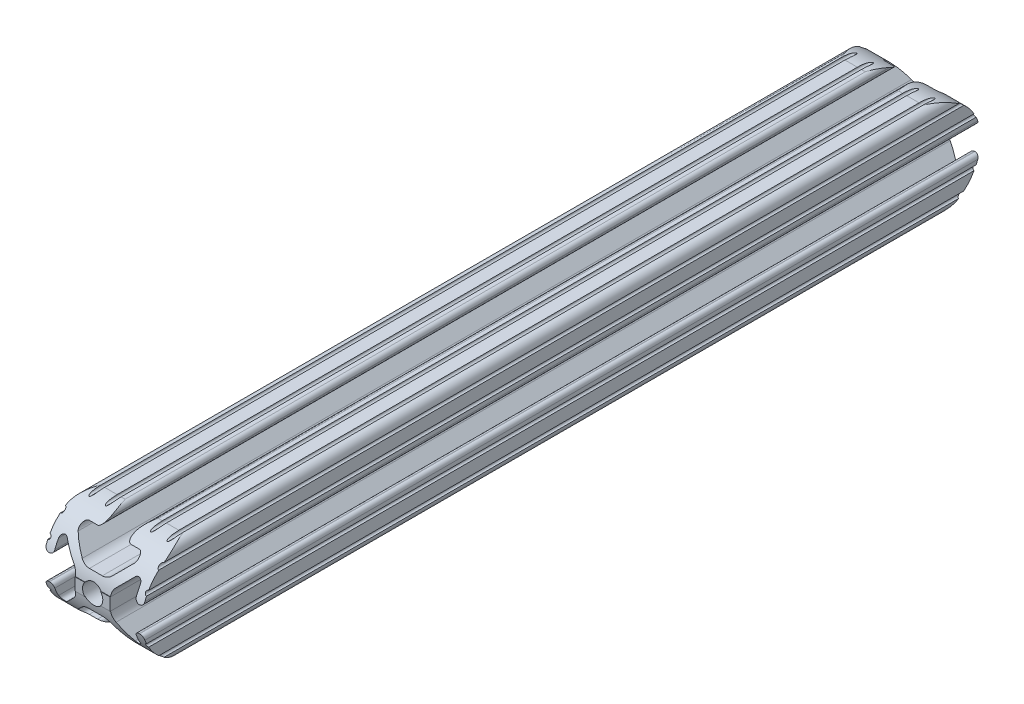
SolidWorks part; units mm, degrees
material "6061 Alloy"
ref_plane "Front Plane" through (0, 0, 0) normal (0, 0, 1) x (1, 0, 0)
ref_plane "Top Plane" through (0, 0, 0) normal (0, 1, 0) x (1, 0, 0)
ref_plane "Right Plane" through (0, 0, 0) normal (1, 0, 0) x (0, 0, -1)
sketch "Sketch1" plane through (0, 0, 0) normal (0, 0, 1) x (1, 0, 0)
  line L88 (-7.1797, -8.6452) -> (-3.9523, -5.4237)
  line L89 (-1.7093, -4.4958) -> (1.7093, -4.4958)
  line L90 (3.9523, -5.4237) -> (7.1797, -8.6452)
  line L91 (6.4164, -10.4902) -> (4.2875, -10.4902)
  line L92 (3.2385, -11.5392) -> (3.2385, -11.651)
  line L93 (4.2875, -12.7) -> (5.3171, -12.7)
  line L94 (6.3331, -12.7) -> (9.5504, -12.7)
  line L95 (12.7, -9.5504) -> (12.7, -6.3331)
  line L96 (12.7, -5.3171) -> (12.7, -4.2875)
  line L97 (11.651, -3.2385) -> (11.5392, -3.2385)
  line L98 (10.4902, -4.2875) -> (10.4902, -6.4021)
  line L99 (8.7371, -7.1294) -> (5.441, -3.8408)
  line L100 (4.5085, -1.5932) -> (4.5085, 1.5932)
  line L101 (5.441, 3.8408) -> (8.7371, 7.1294)
  line L102 (10.4902, 6.4021) -> (10.4902, 4.2875)
  line L103 (11.5392, 3.2385) -> (11.651, 3.2385)
  line L104 (12.7, 4.2875) -> (12.7, 5.3171)
  line L105 (12.7, 6.3331) -> (12.7, 9.5504)
  line L106 (9.5504, 12.7) -> (6.3331, 12.7)
  line L107 (5.3171, 12.7) -> (4.2875, 12.7)
  line L108 (3.2385, 11.651) -> (3.2385, 11.5392)
  line L109 (4.2875, 10.4902) -> (6.4768, 10.4902)
  line L110 (7.207, 8.7244) -> (3.8983, 5.4232)
  line L111 (1.6558, 4.4958) -> (-1.6558, 4.4958)
  line L112 (-3.8983, 5.4232) -> (-7.207, 8.7244)
  line L113 (-6.4768, 10.4902) -> (-4.2875, 10.4902)
  line L114 (-3.2385, 11.5392) -> (-3.2385, 11.651)
  line L115 (-4.2875, 12.7) -> (-5.3171, 12.7)
  line L116 (-6.3331, 12.7) -> (-9.5504, 12.7)
  line L117 (-12.7, 9.5504) -> (-12.7, 6.3331)
  line L118 (-12.7, 5.3171) -> (-12.7, 4.2875)
  line L119 (-11.651, 3.2385) -> (-11.5392, 3.2385)
  line L120 (-10.4902, 4.2875) -> (-10.4902, 6.4021)
  line L121 (-8.7371, 7.1294) -> (-5.441, 3.8408)
  line L122 (-4.5085, 1.5932) -> (-4.5085, -1.5932)
  line L123 (-5.441, -3.8408) -> (-8.7371, -7.1294)
  line L124 (-10.4902, -6.4021) -> (-10.4902, -4.2875)
  line L125 (-11.5392, -3.2385) -> (-11.651, -3.2385)
  line L126 (-12.7, -4.2875) -> (-12.7, -5.3171)
  line L127 (-12.7, -6.3331) -> (-12.7, -9.5504)
  line L128 (-9.5504, -12.7) -> (-6.3331, -12.7)
  line L129 (-5.3171, -12.7) -> (-4.2875, -12.7)
  line L130 (-3.2385, -11.651) -> (-3.2385, -11.5392)
  line L131 (-4.2875, -10.4902) -> (-6.4164, -10.4902)
  circle A1 centre (0, 0) radius 2.6035
  arc A104 (-7.1797, -8.6452) -> (-6.4164, -10.4902) centre (-6.4164, -9.4098) ccw
  arc A105 (-1.7093, -4.4958) -> (-3.9523, -5.4237) centre (-1.7093, -7.6708) ccw
  arc A106 (3.9523, -5.4237) -> (1.7093, -4.4958) centre (1.7093, -7.6708) ccw
  arc A107 (6.4164, -10.4902) -> (7.1797, -8.6452) centre (6.4164, -9.4098) ccw
  arc A108 (4.2875, -10.4902) -> (3.2385, -11.5392) centre (4.2875, -11.5392) ccw
  arc A109 (3.2385, -11.651) -> (4.2875, -12.7) centre (4.2875, -11.651) ccw
  arc A110 (6.3331, -12.7) -> (5.3171, -12.7) centre (5.8251, -12.7) ccw
  arc A111 (10.5664, -12.6998) -> (9.5504, -12.7) centre (10.0584, -12.7) ccw
  arc A112 (10.5664, -12.6998) -> (12.6998, -10.5664) centre (10.5918, -10.5918) ccw
  arc A113 (12.7, -9.5504) -> (12.6998, -10.5664) centre (12.7, -10.0584) ccw
  arc A114 (12.7, -5.3171) -> (12.7, -6.3331) centre (12.7, -5.8251) ccw
  arc A115 (12.7, -4.2875) -> (11.651, -3.2385) centre (11.651, -4.2875) ccw
  arc A116 (11.5392, -3.2385) -> (10.4902, -4.2875) centre (11.5392, -4.2875) ccw
  arc A117 (8.7371, -7.1294) -> (10.4902, -6.4021) centre (9.4628, -6.4021) ccw
  arc A118 (4.5085, -1.5932) -> (5.441, -3.8408) centre (7.6835, -1.5932) ccw
  arc A119 (5.441, 3.8408) -> (4.5085, 1.5932) centre (7.6835, 1.5932) ccw
  arc A120 (10.4902, 6.4021) -> (8.7371, 7.1294) centre (9.4628, 6.4021) ccw
  arc A121 (10.4902, 4.2875) -> (11.5392, 3.2385) centre (11.5392, 4.2875) ccw
  arc A122 (11.651, 3.2385) -> (12.7, 4.2875) centre (11.651, 4.2875) ccw
  arc A123 (12.7, 6.3331) -> (12.7, 5.3171) centre (12.7, 5.8251) ccw
  arc A124 (12.6998, 10.5664) -> (12.7, 9.5504) centre (12.7, 10.0584) ccw
  arc A125 (12.6998, 10.5664) -> (10.5664, 12.6998) centre (10.5918, 10.5918) ccw
  arc A126 (9.5504, 12.7) -> (10.5664, 12.6998) centre (10.0584, 12.7) ccw
  arc A127 (5.3171, 12.7) -> (6.3331, 12.7) centre (5.8251, 12.7) ccw
  arc A128 (4.2875, 12.7) -> (3.2385, 11.651) centre (4.2875, 11.651) ccw
  arc A129 (3.2385, 11.5392) -> (4.2875, 10.4902) centre (4.2875, 11.5392) ccw
  arc A130 (7.207, 8.7244) -> (6.4768, 10.4902) centre (6.4768, 9.4563) ccw
  arc A131 (1.6558, 4.4958) -> (3.8983, 5.4232) centre (1.6558, 7.6708) ccw
  arc A132 (-3.8983, 5.4232) -> (-1.6558, 4.4958) centre (-1.6558, 7.6708) ccw
  arc A133 (-6.4768, 10.4902) -> (-7.207, 8.7244) centre (-6.4768, 9.4563) ccw
  arc A134 (-4.2875, 10.4902) -> (-3.2385, 11.5392) centre (-4.2875, 11.5392) ccw
  arc A135 (-3.2385, 11.651) -> (-4.2875, 12.7) centre (-4.2875, 11.651) ccw
  arc A136 (-6.3331, 12.7) -> (-5.3171, 12.7) centre (-5.8251, 12.7) ccw
  arc A137 (-10.5664, 12.6998) -> (-9.5504, 12.7) centre (-10.0584, 12.7) ccw
  arc A138 (-10.5664, 12.6998) -> (-12.6998, 10.5664) centre (-10.5918, 10.5918) ccw
  arc A139 (-12.7, 9.5504) -> (-12.6998, 10.5664) centre (-12.7, 10.0584) ccw
  arc A140 (-12.7, 5.3171) -> (-12.7, 6.3331) centre (-12.7, 5.8251) ccw
  arc A141 (-12.7, 4.2875) -> (-11.651, 3.2385) centre (-11.651, 4.2875) ccw
  arc A142 (-11.5392, 3.2385) -> (-10.4902, 4.2875) centre (-11.5392, 4.2875) ccw
  arc A143 (-8.7371, 7.1294) -> (-10.4902, 6.4021) centre (-9.4628, 6.4021) ccw
  arc A144 (-4.5085, 1.5932) -> (-5.441, 3.8408) centre (-7.6835, 1.5932) ccw
  arc A145 (-5.441, -3.8408) -> (-4.5085, -1.5932) centre (-7.6835, -1.5932) ccw
  arc A146 (-10.4902, -6.4021) -> (-8.7371, -7.1294) centre (-9.4628, -6.4021) ccw
  arc A147 (-10.4902, -4.2875) -> (-11.5392, -3.2385) centre (-11.5392, -4.2875) ccw
  arc A148 (-11.651, -3.2385) -> (-12.7, -4.2875) centre (-11.651, -4.2875) ccw
  arc A149 (-12.7, -6.3331) -> (-12.7, -5.3171) centre (-12.7, -5.8251) ccw
  arc A150 (-12.6998, -10.5664) -> (-12.7, -9.5504) centre (-12.7, -10.0584) ccw
  arc A151 (-12.6998, -10.5664) -> (-10.5664, -12.6998) centre (-10.5918, -10.5918) ccw
  arc A152 (-9.5504, -12.7) -> (-10.5664, -12.6998) centre (-10.0584, -12.7) ccw
  arc A153 (-5.3171, -12.7) -> (-6.3331, -12.7) centre (-5.8251, -12.7) ccw
  arc A154 (-4.2875, -12.7) -> (-3.2385, -11.651) centre (-4.2875, -11.651) ccw
  arc A155 (-3.2385, -11.5392) -> (-4.2875, -10.4902) centre (-4.2875, -11.5392) ccw
extrude "Boss-Extrude1" add sketch "Sketch1" along normal mid plane 215.9
sketch "Sketch2" plane through (4.5085, 0, 0) normal (1, 0, 0) x (0, 0, -1)
  line L0 (-107.95, -1.5932) -> (-107.95, 1.5932) construction
  line L1 (-107.95, -12.6998) -> (107.95, -12.6998) construction
  line L2 (-107.95, 0) -> (-107.95, -12.7)
  line L3 (-107.95, -12.7) -> (-95.25, -12.7)
  line L4 (-107.95, -12.7) -> (107.95, -12.7) construction
  line L5 (-107.95, 12.6998) -> (107.95, 12.6998) construction
  line L6 (-95.3122, 12.6998) -> (-107.95, 12.7) construction
  line L7 (-107.95, 12.7) -> (-107.95, 0)
  line L8 (-107.95, 12.7) -> (107.95, 12.7) construction
  line L9 (-107.95, 12.7) -> (-107.95, 13.97)
  line L10 (-107.95, 13.97) -> (-95.3122, 13.97)
  line L11 (-95.3122, 13.97) -> (-95.3122, 12.6998)
  circle A0 centre (-95.25, 0) radius 3.175
  circle A1 centre (-69.85, 0) radius 3.175
  arc A2 (-107.95, 0) -> (-95.25, -12.7) centre (-95.25, 0) ccw
  arc A3 (-107.95, 0) -> (-95.3122, 12.6998) centre (-95.25, 0) cw
  line M4 (107.95, 1.5932) -> (-107.95, 1.5932)
  line M6 (-107.95, -1.5932) -> (107.95, -1.5932)
  dimension "D1" = 6.35
  dimension "D2" = 12.7
  dimension "D3" = 12.6998
  dimension "D4" = 25.4
  dimension "D5" = 1.27
extrude "Cut-Extrude1" cut sketch "Sketch2" against normal through all both and the other way through all contours A3 L6 L7 M4 | A2 L2 L3 M6 | A0 M4 M6 | A1 M4 M6 | A1 M4 | A1 M6 | A0 M6 | A0 M4 | L6 L11 L10 L9 region at (4.5085, -9.8766, 105.1089) region at (4.5085, 9.8765, 105.1091) region at (4.5085, 13.335, 101.631) region at (4.5085, -2.2417, 95.25) region at (4.5085, 0, 95.25) region at (4.5085, 2.2417, 95.25) region at (4.5085, -2.2417, 69.85) region at (4.5085, 0, 69.85) region at (4.5085, 2.2417, 69.85)
sketch "Sketch3" plane through (4.5085, 0, 0) normal (1, 0, 0) x (0, 0, -1)
  line L0 (107.95, 6.3331) -> (107.95, 9.5504) construction
  line L1 (107.95, -1.5932) -> (107.95, 1.5932) construction
  line L2 (-95.3122, 12.7) -> (107.95, 12.7) construction
  line L3 (95.25, 12.7) -> (107.95, 12.7)
  line L4 (107.95, 12.7) -> (107.95, -12.7)
  line L5 (107.95, -12.7) -> (95.25, -12.7)
  circle A0 centre (95.25, 0) radius 12.7 construction
  arc A1 (95.25, 12.7) -> (95.25, -12.7) centre (95.25, 0) cw
  line M2 (107.95, 1.5932) -> (-67.1037, 1.5932)
  line M4 (-67.1037, -1.5932) -> (107.95, -1.5932)
  dimension "D1" = 12.7
extrude "Cut-Extrude2" cut sketch "Sketch3" against normal through all both and the other way through all contours L3 A1 L4 M2 | A1 L5 L4 M4 region at (4.5085, 9.8766, -105.1089) region at (4.5085, -9.8766, -105.1089)
